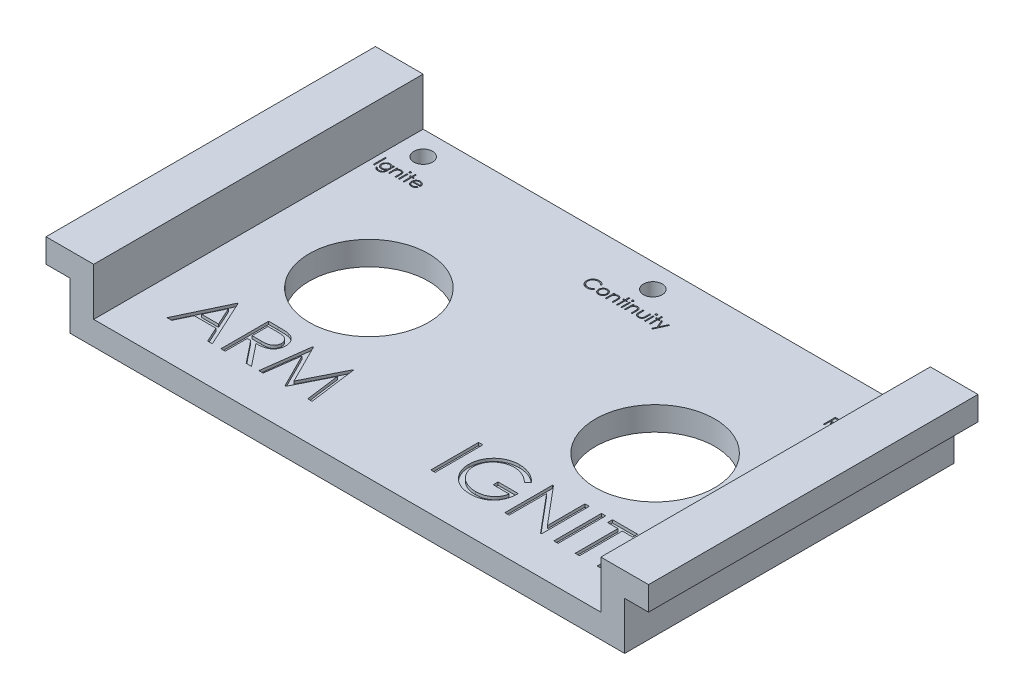
SolidWorks part; units mm, degrees
ref_plane "Front Plane" through (0, 0, 0) normal (0, 0, 1) x (1, 0, 0)
ref_plane "Top Plane" through (0, 0, 0) normal (0, 1, 0) x (1, 0, 0)
ref_plane "Right Plane" through (0, 0, 0) normal (1, 0, 0) x (0, 0, -1)
sketch "Çizim1" plane through (0, 0, 0) normal (0, 1, 0) x (1, 0, 0)
  line L1 (-73.85, -43.85) -> (73.85, -43.85)
  line L2 (-73.85, -43.85) -> (-73.85, 43.85)
  line L3 (-73.85, 43.85) -> (73.85, 43.85)
  line L4 (73.85, -43.85) -> (73.85, 43.85)
  line L5 (-73.85, -43.85) -> (73.85, 43.85) construction
  line L6 (-73.85, 43.85) -> (73.85, -43.85) construction
  point P0 (0, 0)
  dimension "D1" = 147.7
  dimension "D2" = 87.7
extrude "Yükseklik-Ekstrüzyon1" add sketch "Çizim1" along normal blind 6.35
sketch "Çizim2" plane through (-73.85, 0, 0) normal (-1, 0, 0) x (0, 0, 1)
  line L1 (-43.85, 6.35) -> (43.85, 6.35)
  line L2 (-43.85, 6.35) -> (-43.85, 19.05)
  line L3 (-43.85, 19.05) -> (43.85, 19.05)
  line L4 (43.85, 6.35) -> (43.85, 19.05)
  dimension "D1" = 87.7
  dimension "D2" = 12.7
extrude "Yükseklik-Ekstrüzyon2" add sketch "Çizim2" against normal blind 6.35
sketch "Çizim3" plane through (73.85, 0, 0) normal (1, 0, 0) x (0, 0, -1)
  line L1 (-43.85, 6.35) -> (43.85, 6.35)
  line L2 (-43.85, 6.35) -> (-43.85, 19.05)
  line L3 (-43.85, 19.05) -> (43.85, 19.05)
  line L4 (43.85, 6.35) -> (43.85, 19.05)
extrude "Yükseklik-Ekstrüzyon3" add sketch "Çizim3" against normal blind 6.35
sketch "Çizim4" plane through (73.85, 0, 0) normal (1, 0, 0) x (0, 0, -1)
  line L0 (43.85, 19.05) -> (43.85, 0) construction
  line L1 (-43.85, 19.05) -> (43.85, 19.05)
  line L2 (-43.85, 19.05) -> (-43.85, 12.7)
  line L3 (-43.85, 12.7) -> (43.85, 12.7)
  line L4 (43.85, 19.05) -> (43.85, 12.7)
  dimension "D1" = 6.35
sketch "Çizim6" plane through (-73.85, 0, 0) normal (-1, 0, 0) x (0, 0, 1)
  line L1 (-43.85, 19.05) -> (43.85, 19.05)
  line L2 (-43.85, 19.05) -> (-43.85, 12.7)
  line L3 (-43.85, 12.7) -> (43.85, 12.7)
  line L4 (43.85, 19.05) -> (43.85, 12.7)
extrude "Yükseklik-Ekstrüzyon4" add sketch "Çizim6" along normal blind 6.35
extrude "Yükseklik-Ekstrüzyon5" add sketch "Çizim4" along normal blind 6.35
sketch "Çizim7" plane through (0, 6.35, 0) normal (0, 1, 0) x (1, 0, 0)
  circle A0 centre (-38.1, 0) radius 15.875
  dimension "D1" = 31.75
  dimension "D2" = 38.1
extrude "Kes-Ekstrüzyon1" cut sketch "Çizim7" against normal blind 6.35
sketch "Çizim8" plane through (0, 6.35, 0) normal (0, 1, 0) x (1, 0, 0)
  circle A0 centre (38.1, 0) radius 15.875
  dimension "D1" = 31.75
  dimension "D2" = 38.1
extrude "Kes-Ekstrüzyon2" cut sketch "Çizim8" against normal blind 6.35
sketch "Çizim9" plane through (0, 6.35, 0) normal (0, 1, 0) x (1, 0, 0)
  line L0 (67.5, 43.85) -> (-67.5, 43.85) construction
  line L1 (67.5, 43.85) -> (67.5, -43.85) construction
  circle A0 centre (61.15, 37.5) radius 2.5
  dimension "D1" = 5
  dimension "D2" = 6.35
  dimension "D3" = 6.35
extrude "Kes-Ekstrüzyon3" cut sketch "Çizim9" against normal blind 6.35
sketch "Çizim10" plane through (0, 6.35, 0) normal (0, 1, 0) x (1, 0, 0)
  line L0 (67.5, 43.85) -> (-67.5, 43.85) construction
  circle A0 centre (0, 37.5) radius 2.5
  dimension "D1" = 5
  dimension "D2" = 6.35
extrude "Kes-Ekstrüzyon4" cut sketch "Çizim10" against normal blind 6.35
sketch "Çizim11" plane through (0, 6.35, 0) normal (0, 1, 0) x (1, 0, 0)
  line L0 (67.5, 43.85) -> (-67.5, 43.85) construction
  text T0 "Continuity"
  dimension "D1" = 14.732
extrude "Kes-Ekstrüzyon5" cut sketch "Çizim11" against normal blind 0.762
sketch "Çizim12" plane through (0, 6.35, 0) normal (0, 1, 0) x (1, 0, 0)
  line L0 (67.5, 43.85) -> (-67.5, 43.85) construction
  text T0 "Radio"
  dimension "D1" = 14.732
extrude "Kes-Ekstrüzyon6" cut sketch "Çizim12" against normal blind 0.762
sketch "Çizim13" plane through (0, 6.35, 0) normal (0, 1, 0) x (1, 0, 0)
  line L0 (-67.5, -43.85) -> (67.5, -43.85) construction
  text T0 "ARM" font "Century Gothic" height 12.7
  dimension "D1" = 10.16
sketch "Çizim14" plane through (0, 6.35, 0) normal (0, 1, 0) x (1, 0, 0)
  line L0 (-67.5, -43.85) -> (67.5, -43.85) construction
  text T0 "IGNITE" font "Century Gothic" height 12.7
  dimension "D1" = 10.16
extrude "Kes-Ekstrüzyon7" cut sketch "Çizim13" against normal blind 0.762
extrude "Kes-Ekstrüzyon8" cut sketch "Çizim14" against normal blind 0.762
sketch "Çizim15" plane through (0, 6.35, 0) normal (0, 1, 0) x (1, 0, 0)
  line L0 (67.5, 43.85) -> (-67.5, 43.85) construction
  line L1 (-67.5, -43.85) -> (-67.5, 43.85) construction
  circle A0 centre (-61.15, 37.5) radius 2.5
  dimension "D1" = 5
  dimension "D2" = 6.35
  dimension "D3" = 6.35
extrude "Kes-Ekstrüzyon9" cut sketch "Çizim15" against normal blind 6.35
sketch "Çizim16" plane through (0, 6.35, 0) normal (0, 1, 0) x (1, 0, 0)
  line L0 (67.5, 43.85) -> (-67.5, 43.85) construction
  text T0 "Ignite"
  point P1 (-66.4247, 29.9644)
  dimension "D1" = 14.732
extrude "Kes-Ekstrüzyon10" cut sketch "Çizim16" against normal blind 0.762
